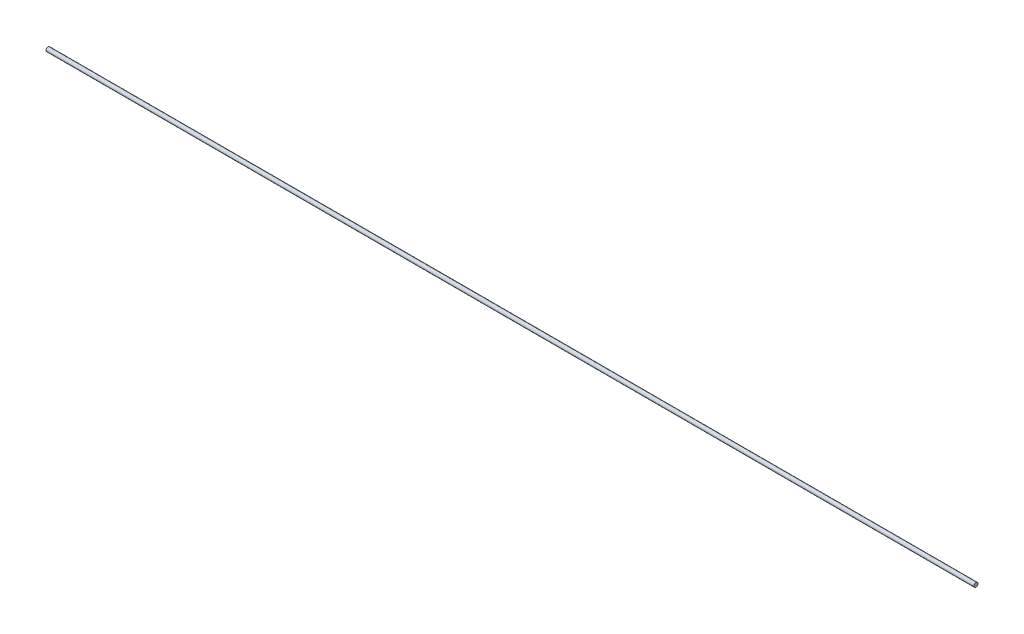
SolidWorks part; units mm, degrees
ref_plane "Front" through (0, 0, 0) normal (0, 0, 1) x (1, 0, 0)
ref_plane "Top" through (0, 0, 0) normal (0, 1, 0) x (1, 0, 0)
ref_plane "Right" through (0, 0, 0) normal (1, 0, 0) x (0, 0, -1)
sketch "Sketch1" plane through (0, 0, 0) normal (0, 0, 1) x (1, 0, 0)
  line L0 (0, 0) -> (34.3951, 0) construction
  line L1 (0, 0) -> (0, 3.175)
  line L2 (0, 3.175) -> (1445.7224, 3.175)
  line L3 (1445.7224, 3.175) -> (1445.7224, 0)
  line L4 (1445.7224, 0) -> (0, 0)
  line L5 (1445.7224, 3.25) -> (1445.7224, -3.25) construction
  dimension "D1" = 6.35
revolve "Revolve1" add sketch "Sketch1" angle 360 about L0
